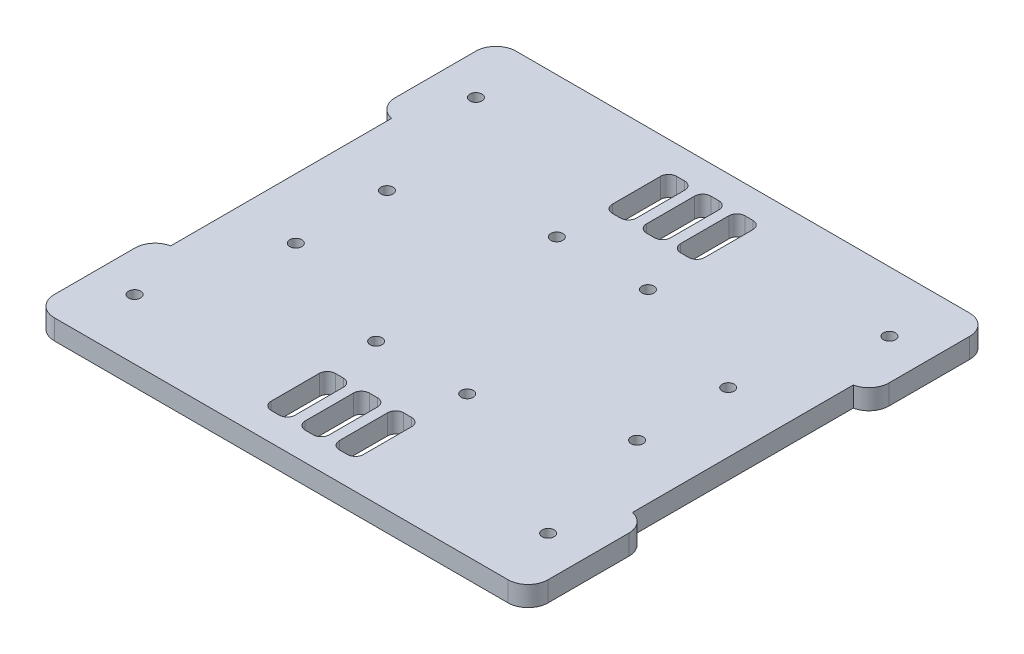
SolidWorks part; units mm, degrees
material "Acrílico (médio-alto impacto)"
ref_plane "Plano frontal" through (0, 0, 0) normal (0, 0, 1) x (1, 0, 0)
ref_plane "Plano superior" through (0, 0, 0) normal (0, 1, 0) x (1, 0, 0)
ref_plane "Plano direito" through (0, 0, 0) normal (1, 0, 0) x (0, 0, -1)
sketch "Esboço1" plane through (0, 0, 0) normal (0, 1, 0) x (1, 0, 0)
  line L0 (81.9059, -20.4292) -> (85.9059, -20.4292)
  line L1 (-32.0941, 9.5708) -> (80.9059, 9.5708)
  line L2 (-37.0941, 4.5708) -> (-37.0941, -20.4292)
  line L3 (-37.0941, -20.4292) -> (-33.0941, -20.4292)
  line L4 (85.9059, 4.5708) -> (85.9059, -20.4292)
  line L6 (-33.0941, -20.4292) -> (-33.0941, -75.4292)
  line L8 (81.9059, -20.4292) -> (81.9059, -75.4292)
  line L9 (-37.0941, -75.4292) -> (-33.0941, -75.4292)
  line L10 (-37.0941, -75.4292) -> (-37.0941, -100.4292)
  line L11 (-32.0941, -105.4292) -> (80.9059, -105.4292)
  line L12 (85.9059, -75.4292) -> (85.9059, -100.4292)
  line L13 (81.9059, -75.4292) -> (85.9059, -75.4292)
  arc A0 (-32.0941, 9.5708) -> (-37.0941, 4.5708) centre (-32.0941, 4.5708) ccw
  arc A1 (80.9059, 9.5708) -> (85.9059, 4.5708) centre (80.9059, 4.5708) cw
  arc A2 (80.9059, -105.4292) -> (85.9059, -100.4292) centre (80.9059, -100.4292) ccw
  arc A3 (-37.0941, -100.4292) -> (-32.0941, -105.4292) centre (-32.0941, -100.4292) ccw
  point P14 (-37.0941, 9.5708)
  point P19 (85.9059, -105.4292)
  point P22 (-37.0941, -105.4292)
  dimension "D9" = 5
  dimension "D1" = 30
  dimension "D2" = 123
  dimension "D3" = 115
  dimension "D4" = 55
  dimension "D5" = 4
  dimension "D6" = 4
  dimension "D7" = 123
  dimension "D8" = 30
extrude "Ressalto-extrusão1" add sketch "Esboço1" along normal blind 5
fillet "Filete1" radius 5 4 edges at (-37.0941, 2.5, 75.4292) (-37.0941, 2.5, 20.4292) (85.9059, 2.5, 20.4292) (85.9059, 2.5, 75.4292)
sketch "Esboço3" plane through (0, 0, 0) normal (0, -1, 0) x (1, 0, 0)
  line L0 (-37.0941, -4.5708) -> (-37.0941, 15.5302) construction
  line L1 (80.9059, -9.5708) -> (-32.0941, -9.5708) construction
  line L2 (85.9059, 15.5302) -> (85.9059, -4.5708) construction
  line L3 (-33.0941, 47.9292) -> (81.9059, 47.9292) construction
  line L4 (-33.0941, 20.4292) -> (-33.0941, 75.4292) construction
  line L5 (81.9059, 75.4292) -> (81.9059, 20.4292) construction
  line L6 (35.9059, 84.4292) -> (35.9059, 96.4292)
  line L7 (14.9059, 13.4292) -> (16.9059, 13.4292)
  line L8 (12.9059, 11.4292) -> (12.9059, -0.5708)
  line L9 (14.9059, -2.5708) -> (16.9059, -2.5708)
  line L10 (18.9059, 11.4292) -> (18.9059, -0.5708)
  line L11 (23.4059, 13.4292) -> (25.4059, 13.4292)
  line L12 (21.4059, 11.4292) -> (21.4059, -0.5708)
  line L13 (23.4059, -2.5708) -> (25.4059, -2.5708)
  line L14 (27.4059, 11.4292) -> (27.4059, -0.5708)
  line L15 (31.9059, 13.4292) -> (33.9059, 13.4292)
  line L16 (29.9059, 11.4292) -> (29.9059, -0.5708)
  line L17 (31.9059, -2.5708) -> (33.9059, -2.5708)
  line L18 (35.9059, 11.4292) -> (35.9059, -0.5708)
  line L19 (31.9059, 98.4292) -> (33.9059, 98.4292)
  line L20 (29.9059, 84.4292) -> (29.9059, 96.4292)
  line L21 (31.9059, 82.4292) -> (33.9059, 82.4292)
  line L22 (27.4059, 84.4292) -> (27.4059, 96.4292)
  line L23 (23.4059, 98.4292) -> (25.4059, 98.4292)
  line L24 (21.4059, 84.4292) -> (21.4059, 96.4292)
  line L25 (23.4059, 82.4292) -> (25.4059, 82.4292)
  line L26 (18.9059, 84.4292) -> (18.9059, 96.4292)
  line L27 (14.9059, 98.4292) -> (16.9059, 98.4292)
  line L28 (12.9059, 84.4292) -> (12.9059, 96.4292)
  line L29 (14.9059, 82.4292) -> (16.9059, 82.4292)
  circle A0 centre (-27.0941, 5.4292) radius 1.5
  circle A1 centre (75.9059, 5.4292) radius 1.5
  arc A2 (31.9059, 13.4292) -> (29.9059, 11.4292) centre (31.9059, 11.4292) ccw
  arc A3 (33.9059, 13.4292) -> (35.9059, 11.4292) centre (33.9059, 11.4292) cw
  arc A4 (33.9059, -2.5708) -> (35.9059, -0.5708) centre (33.9059, -0.5708) ccw
  arc A5 (29.9059, -0.5708) -> (31.9059, -2.5708) centre (31.9059, -0.5708) ccw
  arc A6 (25.4059, -2.5708) -> (27.4059, -0.5708) centre (25.4059, -0.5708) ccw
  arc A7 (25.4059, 13.4292) -> (27.4059, 11.4292) centre (25.4059, 11.4292) cw
  arc A8 (23.4059, 13.4292) -> (21.4059, 11.4292) centre (23.4059, 11.4292) ccw
  arc A9 (21.4059, -0.5708) -> (23.4059, -2.5708) centre (23.4059, -0.5708) ccw
  arc A10 (14.9059, 13.4292) -> (12.9059, 11.4292) centre (14.9059, 11.4292) ccw
  arc A11 (16.9059, 13.4292) -> (18.9059, 11.4292) centre (16.9059, 11.4292) cw
  arc A12 (16.9059, -2.5708) -> (18.9059, -0.5708) centre (16.9059, -0.5708) ccw
  arc A13 (12.9059, -0.5708) -> (14.9059, -2.5708) centre (14.9059, -0.5708) ccw
  arc A14 (12.9059, 96.4292) -> (14.9059, 98.4292) centre (14.9059, 96.4292) cw
  arc A15 (16.9059, 98.4292) -> (18.9059, 96.4292) centre (16.9059, 96.4292) cw
  arc A16 (16.9059, 82.4292) -> (18.9059, 84.4292) centre (16.9059, 84.4292) ccw
  arc A17 (14.9059, 82.4292) -> (12.9059, 84.4292) centre (14.9059, 84.4292) cw
  arc A18 (21.4059, 96.4292) -> (23.4059, 98.4292) centre (23.4059, 96.4292) cw
  arc A19 (23.4059, 82.4292) -> (21.4059, 84.4292) centre (23.4059, 84.4292) cw
  arc A20 (25.4059, 82.4292) -> (27.4059, 84.4292) centre (25.4059, 84.4292) ccw
  arc A21 (25.4059, 98.4292) -> (27.4059, 96.4292) centre (25.4059, 96.4292) cw
  arc A22 (29.9059, 96.4292) -> (31.9059, 98.4292) centre (31.9059, 96.4292) cw
  arc A23 (33.9059, 98.4292) -> (35.9059, 96.4292) centre (33.9059, 96.4292) cw
  arc A24 (33.9059, 82.4292) -> (35.9059, 84.4292) centre (33.9059, 84.4292) ccw
  arc A25 (31.9059, 82.4292) -> (29.9059, 84.4292) centre (31.9059, 84.4292) cw
  circle A26 centre (75.9059, 90.4292) radius 1.5
  circle A27 centre (-27.0941, 90.4292) radius 1.5
  point P30 (29.9059, 13.4292)
  point P33 (35.9059, 13.4292)
  point P38 (29.9059, -2.5708)
  point P43 (27.4059, 13.4292)
  point P46 (21.4059, 13.4292)
  point P49 (21.4059, -2.5708)
  point P52 (12.9059, 13.4292)
  point P55 (18.9059, 13.4292)
  point P60 (12.9059, -2.5708)
  point P101 (12.9059, 98.4292)
  point P102 (18.9059, 82.4292)
  point P103 (12.9059, 82.4292)
  point P104 (21.4059, 98.4292)
  point P105 (21.4059, 82.4292)
  point P106 (27.4059, 82.4292)
  point P107 (29.9059, 98.4292)
  point P108 (35.9059, 82.4292)
  point P109 (29.9059, 82.4292)
  point P110 (24.4059, -9.5708)
  dimension "D1" = 10
  dimension "D2" = 15
  dimension "D3" = 3
  dimension "D4" = 10
  dimension "D5" = 15
  dimension "D6" = 3
  dimension "D18" = 2
  dimension "D7" = 2.5
  dimension "D8" = 2.5
  dimension "D9" = 6
  dimension "D10" = 6
  dimension "D11" = 6
  dimension "D12" = 50
  dimension "D13" = 50
  dimension "D14" = 16
  dimension "D15" = 16
  dimension "D16" = 16
  dimension "D17" = 7
  dimension "D19" = 7
extrude "Corte-extrusão1" cut sketch "Esboço3" against normal blind 5
sketch "Esboço5" plane through (0, 0, 0) normal (0, -1, 0) x (1, 0, 0)
  line L0 (-33.0941, 20.4292) -> (-33.0941, 75.4292) construction
  line L2 (81.9059, 75.4292) -> (81.9059, 20.4292) construction
  line L3 (80.9059, -9.5708) -> (-32.0941, -9.5708) construction
  line L5 (80.9059, -9.5708) -> (-32.0941, -9.5708) construction
  line L6 (-32.0941, 105.4292) -> (80.9059, 105.4292) construction
  line L7 (81.9059, 47.9292) -> (-33.0941, 47.9292) construction
  line L8 (24.4059, 105.4292) -> (24.4059, -9.5708) construction
  circle A0 centre (13.0559, 25.4292) radius 1.5
  circle A1 centre (35.7559, 25.4292) radius 1.5
  circle A2 centre (-18.0941, 59.2792) radius 1.5
  circle A3 centre (-18.0941, 36.5792) radius 1.5
  circle A4 centre (13.0559, 70.4292) radius 1.5
  circle A5 centre (35.7559, 70.4292) radius 1.5
  circle A6 centre (66.9059, 36.5792) radius 1.5
  circle A7 centre (66.9059, 59.2792) radius 1.5
  dimension "D1" = 22.7
  dimension "D2" = 3
  dimension "D3" = 3
  dimension "D4" = 46.15
  dimension "D5" = 46.15
  dimension "D6" = 35
  dimension "D7" = 22.7
  dimension "D8" = 3
  dimension "D9" = 3
  dimension "D10" = 15
  dimension "D11" = 46.15
  dimension "D12" = 46.15
extrude "Corte-extrusão2" cut sketch "Esboço5" against normal blind 10
